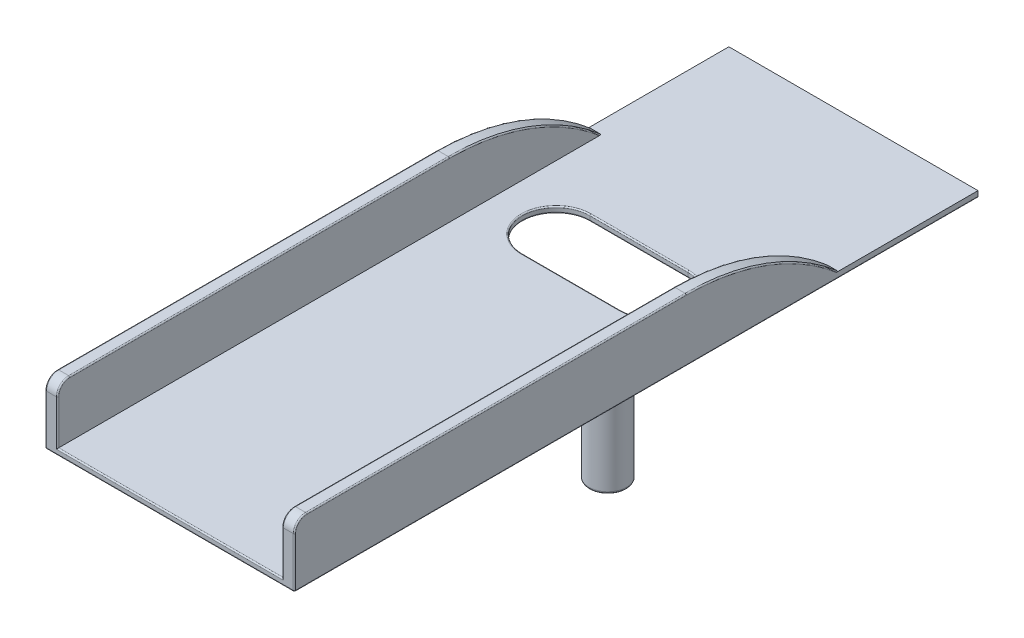
SolidWorks part; units mm, degrees
ref_plane "Front Plane" through (0, 0, 0) normal (0, 0, 1) x (1, 0, 0)
ref_plane "Top Plane" through (0, 0, 0) normal (0, 1, 0) x (1, 0, 0)
ref_plane "Right Plane" through (0, 0, 0) normal (1, 0, 0) x (0, 0, -1)
sketch "Sketch1" plane through (0, 0, 0) normal (0, 1, 0) x (1, 0, 0)
  line L0 (-11.9697, 0) -> (11.9697, 0) construction
  circle A0 centre (-11.9697, 0) radius 3.8735
  circle A1 centre (11.9697, 0) radius 3.8735
  circle A2 centre (-11.9697, 0) radius 2.032
  circle A3 centre (11.9697, 0) radius 2.032
  point P0 (-11.9697, 0)
  point P1 (11.9697, 0)
  point P5 (0, 0)
  dimension "D2" = 7.747
  dimension "D3" = 7.747
  dimension "D4" = 4.064
  dimension "D5" = 4.064
  dimension "D1" = 23.9395
extrude "Boss-Extrude1" add sketch "Sketch1" along normal blind 25.9842
sketch "Sketch2" plane through (0, 25.9842, 0) normal (0, 1, 0) x (1, 0, 0)
  line L0 (-25.8445, 62.8904) -> (-25.8445, -81.2546)
  line L1 (-23.3045, 60.3504) -> (23.2283, 60.3504)
  line L2 (-23.3045, 60.3504) -> (-23.3045, -78.7146)
  line L3 (-23.3045, -78.7146) -> (23.2283, -78.7146)
  line L4 (23.2283, 60.3504) -> (23.2283, -78.7146)
  line L5 (-25.8445, -81.2546) -> (25.7683, -81.2546)
  line L6 (25.7683, 62.8904) -> (25.7683, -81.2546)
  line L7 (-25.8445, 62.8904) -> (25.7683, 62.8904)
  dimension "D1" = 46.5328
  dimension "D2" = 139.065
  dimension "D3" = 60.3504
  dimension "D4" = 2.54
extrude "Boss-Extrude2" add sketch "Sketch2" along normal blind 1.27 contours L6 L5 L0 L7
extrude "Boss-Extrude3" add sketch "Sketch2<3>" along normal blind 12.954
sketch "Sketch2<3>" plane through (0, 25.9842, 0) normal (0, 1, 0) x (1, 0, 0) same geometry as "Sketch2"
sketch "Sketch5" plane through (0, 0, -62.8904) normal (0, 0, -1) x (-1, 0, 0)
  line L0 (-25.7683, 38.9382) -> (-25.7683, 25.9842) construction
  line L1 (25.8445, 38.9382) -> (-25.7683, 38.9382)
  line L2 (25.8445, 38.9382) -> (25.8445, 27.2542)
  line L3 (25.8445, 27.2542) -> (-25.7683, 27.2542)
  line L4 (-25.7683, 38.9382) -> (-25.7683, 27.2542)
  line L5 (25.8445, 25.9842) -> (-25.7683, 25.9842) construction
  dimension "D1" = 1.27
extrude "Cut-Extrude1" cut sketch "Sketch5" against normal blind 28.956
fillet "Fillet1" radius 48.26 2 edges at (24.4983, 38.9382, -33.9344) (-24.5745, 38.9382, -33.9344)
fillet "Fillet2" radius 2.54 2 edges at (25.7683, 32.4612, 81.2546) (-25.8445, 32.4612, 81.2546)
sketch "Sketch6" plane through (0, 0, 78.7146) normal (0, 0, -1) x (-1, 0, 0)
  line L1 (-25.7683, 38.9382) -> (25.8445, 38.9382)
  line L2 (-25.7683, 38.9382) -> (-25.7683, 25.9842)
  line L3 (-25.7683, 25.9842) -> (25.8445, 25.9842)
  line L4 (25.8445, 38.9382) -> (25.8445, 25.9842)
extrude "Cut-Extrude2" cut sketch "Sketch6" against normal blind 44.196
fillet "Fillet3" radius 2.54 2 edges at (-24.5745, 38.9382, 78.7146) (24.4983, 38.9382, 78.7146)
sketch "Sketch7" plane through (0, 25.9842, 0) normal (0, -1, 0) x (1, 0, 0)
  line L0 (-10.16, -11.43) -> (10.16, -11.43) construction
  line L1 (-10.16, -4.445) -> (10.16, -4.445)
  line L2 (-10.16, -18.415) -> (10.16, -18.415)
  arc A0 (-10.16, -4.445) -> (-10.16, -18.415) centre (-10.16, -11.43) ccw
  arc A1 (10.16, -18.415) -> (10.16, -4.445) centre (10.16, -11.43) ccw
  point P2 (0, -11.43)
  point P7 (0, 0)
  dimension "D1" = 11.43
  dimension "D2" = 20.32
  dimension "D3" = 13.97
extrude "Cut-Extrude3" cut sketch "Sketch7" against normal blind 16.256
fillet "Fillet4" radius 0.254 18 edges at (23.2283, 35.923, -19.2416) (23.2283, 38.9382, 36.862) (23.2283, 38.1943, 77.9707) (25.7683, 35.923, -19.2416) (25.7683, 38.9382, 36.862) (25.7683, 38.1943, 77.9707) (-25.8445, 35.923, -19.2416) (-25.8445, 38.9382, 36.862) (-25.8445, 38.1943, 77.9707) (-23.3045, 35.923, -19.2416) (-23.3045, 38.9382, 36.862) (-23.3045, 38.1943, 77.9707) (-0.0381, 27.2542, 78.7146) (23.2283, 31.8262, 78.7146) (25.7683, 31.1912, 78.7146) (-0.0381, 25.9842, 78.7146) (-25.8445, 31.1912, 78.7146) (-23.3045, 31.8262, 78.7146)
fillet "Fillet5" radius 0.254 11 edges at (-25.7701, 26.0586, 78.6402) (25.6939, 26.0586, 78.6402) (-11.9697, 25.9842, 3.8735) (11.9697, 25.9842, 3.8735) (-0.0381, 25.9842, -62.8904) (-25.8445, 25.9842, 7.7851) (25.7683, 25.9842, 7.7851) (0, 25.9842, -18.415) (17.145, 25.9842, -11.43) (0, 25.9842, -4.445) (-17.145, 25.9842, -11.43)
fillet "Fillet6" radius 0.254 4 edges at (17.145, 27.2542, -11.43) (0, 27.2542, -18.415) (-17.145, 27.2542, -11.43) (0, 27.2542, -4.445)
fillet "Fillet7" radius 0.508 2 edges at (-11.9697, 0, 3.8735) (11.9697, 0, 3.8735)
